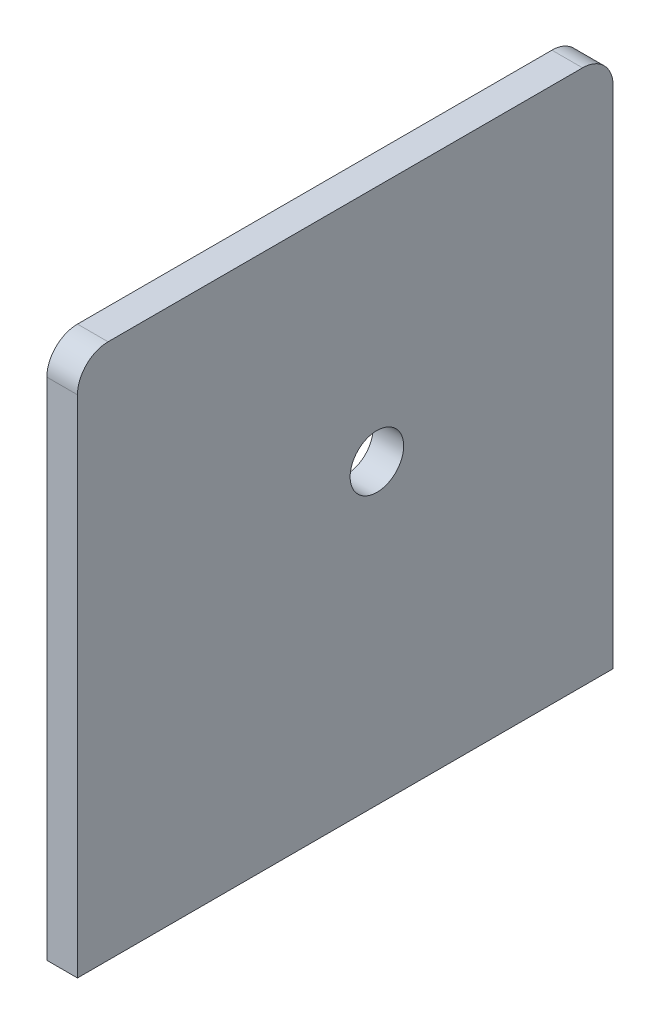
SolidWorks part; units mm, degrees
ref_plane "Front Plane" through (0, 0, 0) normal (0, 0, 1) x (1, 0, 0)
ref_plane "Top Plane" through (0, 0, 0) normal (0, 1, 0) x (1, 0, 0)
ref_plane "Right Plane" through (0, 0, 0) normal (1, 0, 0) x (0, 0, -1)
sketch "Sketch1" plane through (0, 0, 0) normal (0, 1, 0) x (1, 0, 0)
  line L6 (-24.2713, -31.1062) -> (-28.2713, -31.1062)
  line L12 (-24.2713, -31.1062) -> (-24.2713, 38.8938)
  line L13 (-24.2713, 38.8938) -> (-28.2713, 38.8938)
  line L14 (-28.2713, -31.1062) -> (-28.2713, 38.8938)
  dimension "D8" = 4
  dimension "D9" = 70
extrude "Boss-Extrude1" add sketch "Sketch1" along normal blind 3 contours L6 L14 L13 L12 | L14 L6 L12 L13 region at (-26.2713, 0, -3.8938)
extrude "Boss-Extrude2" add sketch "Sketch1<3>" along normal blind 70 rebuild error yes
sketch "Sketch1<3>" plane through (0, 0, 0) normal (0, 1, 0) x (1, 0, 0) same geometry as "Sketch1"
extrude "Boss-Extrude3" add sketch "Sketch1<4>" along normal blind 70 contours L14 L13 L12 L6
sketch "Sketch1<4>" plane through (0, 0, 0) normal (0, 1, 0) x (1, 0, 0) same geometry as "Sketch1"
sketch "Sketch5" plane through (-50.7713, 0, 0) normal (-1, 0, 0) x (0, 0, 1)
  line L0 (-8.0225, 70) -> (-8.0225, 0) construction
  line L5 (-34.2125, 70) -> (-34.2125, 3) construction
  circle A0 centre (-8.0225, 60) radius 4
  dimension "D1" = 60
  dimension "D3" = 8
  dimension "D2" = 26.19
extrude "Cut-Extrude4" cut sketch "Sketch5" against normal blind 10 rebuild error yes
sketch "Sketch6" plane through (0, 3, 0) normal (0, 1, 0) x (1, 0, 0)
  line L0 (-50.7876, 44.2125) -> (49.2124, 44.2125) construction
  line L3 (-50.7876, -35.7875) -> (49.2124, -35.7875) construction
  line L8 (-50.7713, -40.7875) -> (39.2287, -40.7875) construction
  line L9 (-50.7713, 49.2125) -> (39.2287, 49.2125) construction
  circle A0 centre (-45.7876, -35.7875) radius 2.5
  circle A1 centre (-45.7876, 44.2125) radius 2.5
  circle A2 centre (43.7185, 44.2125) radius 2.5
  circle A3 centre (43.7185, -35.7875) radius 2.5
  dimension "D1" = 5
  dimension "D2" = 5
  dimension "D3" = 5
  dimension "D4" = 5
extrude "Cut-Extrude5" cut sketch "Sketch6" against normal blind 10 rebuild error yes
extrude "Boss-Extrude4" add sketch "Sketch1<5>" along normal blind 80 rebuild error yes
sketch "Sketch1<5>" plane through (0, 0, 0) normal (0, 1, 0) x (1, 0, 0) same geometry as "Sketch1"
extrude "Cut-Extrude6" cut sketch "Sketch5<2>" against normal blind 10 rebuild error yes
sketch "Sketch5<2>" plane through (-50.7713, 0, 0) normal (-1, 0, 0) x (0, 0, 1) same geometry as "Sketch5"
fillet "Fillet1" radius 3 rebuild error yes
fillet "Fillet2" radius 5 rebuild error yes
fillet "Fillet3" radius 4 2 edges at (-26.2713, 70, -38.8938) (-26.2713, 70, 31.1062)
sketch "Sketch7" plane through (39.2287, 0, 0) normal (1, 0, 0) x (0, 0, -1)
  line L0 (-30.7875, -10) -> (39.2125, -10) construction
  line L1 (-30.7875, 65) -> (-30.7875, 3) construction
  line L2 (39.2125, 65) -> (39.2125, 3) construction
  line L3 (-37.7875, 0) -> (46.2125, 0) construction
  circle A0 centre (27.4823, -10) radius 2.5
  dimension "D1" = 10
extrude "Cut-Extrude7" cut sketch "Sketch7" against normal blind 10 rebuild error yes
sketch "Sketch8" plane through (39.2287, 0, 0) normal (1, 0, 0) x (0, 0, -1)
  line L0 (39.2125, 20) -> (-30.7875, 20) construction
  line L1 (39.2125, 65) -> (39.2125, 3) construction
  line L2 (-30.7875, 65) -> (-30.7875, 3) construction
  line L3 (26.9146, 20) -> (8.0207, 38.8939) construction
  circle A0 centre (8.0207, 38.8939) radius 2.5
  dimension "D3" = 5
  dimension "D1" = 26.72
  dimension "D2" = 45
extrude "Cut-Extrude8" cut sketch "Sketch8" against normal blind 10 rebuild error yes
sketch "Sketch9" plane through (39.2287, 0, 0) normal (1, 0, 0) x (0, 0, -1)
  circle A0 centre (8.0207, 38.8939) radius 3.5
  dimension "D1" = 7
extrude "Cut-Extrude9" cut sketch "Sketch9" against normal up to surface (67.5 mm away) up to face at (-28.2713, 45.6095, -3.8938)
sketch "Sketch26" plane through (0, 3, 0) normal (0, 1, 0) x (1, 0, 0)
  line L0 (39.2287, 39.2125) -> (39.2287, 46.2125) construction
  line L1 (39.2287, -37.7875) -> (39.2287, -30.7875) construction
  circle A0 centre (34.2287, 44.2125) radius 2.5
  circle A2 centre (34.2287, -36.0634) radius 2.5
  dimension "D1" = 5
  dimension "D2" = 5
  dimension "D3" = 5
  dimension "D4" = 5
extrude "Cut-Extrude11" cut sketch "Sketch26" against normal blind 10 contours A2 | A0 rebuild error yes
sketch "Sketch27" plane through (0, 3, 0) normal (0, 1, 0) x (1, 0, 0)
  line L0 (-49.8926, 48.3339) -> (38.35, -39.9088) construction
  line L1 (38.35, 48.3339) -> (-49.8926, -39.9088) construction
  line L2 (7.7287, 4.2125) -> (-19.2713, 4.2125) construction
  line L3 (7.7287, 3.4625) -> (-19.2713, 3.4625)
  line L4 (7.7287, 4.9625) -> (-19.2713, 4.9625)
  line L5 (0.9787, -7.4788) -> (-12.5213, 15.9039) construction
  line L6 (0.3292, -7.8538) -> (-13.1708, 15.5289)
  line L7 (1.6282, -7.1038) -> (-11.8718, 16.2789)
  line L8 (-12.5213, -7.4788) -> (0.9787, 15.9039) construction
  line L9 (-13.1708, -7.1038) -> (0.3292, 16.2789)
  line L10 (-11.8718, -7.8538) -> (1.6282, 15.5289)
  line L11 (-19.2713, 4.2125) -> (7.7287, 4.2125) construction
  line L12 (-19.2713, 4.9625) -> (7.7287, 4.9625)
  line L13 (-19.2713, 3.4625) -> (7.7287, 3.4625)
  line L14 (-12.5213, 15.9039) -> (0.9787, -7.4788) construction
  line L15 (-11.8718, 16.2789) -> (1.6282, -7.1038)
  line L16 (-13.1708, 15.5289) -> (0.3292, -7.8538)
  line L17 (0.9787, 15.9039) -> (-12.5213, -7.4788) construction
  line L18 (1.6282, 15.5289) -> (-11.8718, -7.8538)
  line L19 (0.3292, 16.2789) -> (-13.1708, -7.1038)
  arc A0 (-47.7713, 49.2125) -> (-50.7713, 46.2125) centre (-47.7713, 46.2125) ccw construction
  arc A1 (36.2287, -40.7875) -> (39.2287, -37.7875) centre (36.2287, -37.7875) ccw construction
  arc A2 (39.2287, 46.2125) -> (36.2287, 49.2125) centre (36.2287, 46.2125) ccw construction
  arc A3 (-50.7713, -37.7875) -> (-47.7713, -40.7875) centre (-47.7713, -37.7875) ccw construction
  arc A4 (7.7287, 3.4625) -> (7.7287, 4.9625) centre (7.7287, 4.2125) ccw
  arc A5 (-19.2713, 4.9625) -> (-19.2713, 3.4625) centre (-19.2713, 4.2125) ccw
  circle A9 centre (-5.7713, 4.2125) radius 5.375
  arc A10 (0.3292, -7.8538) -> (1.6282, -7.1038) centre (0.9787, -7.4788) ccw
  arc A11 (-11.8718, 16.2789) -> (-13.1708, 15.5289) centre (-12.5213, 15.9039) ccw
  arc A12 (-13.1708, -7.1038) -> (-11.8718, -7.8538) centre (-12.5213, -7.4788) ccw
  arc A13 (1.6282, 15.5289) -> (0.3292, 16.2789) centre (0.9787, 15.9039) ccw
  arc A14 (-19.2713, 4.9625) -> (-19.2713, 3.4625) centre (-19.2713, 4.2125) ccw
  arc A15 (7.7287, 3.4625) -> (7.7287, 4.9625) centre (7.7287, 4.2125) ccw
  arc A16 (-11.8718, 16.2789) -> (-13.1708, 15.5289) centre (-12.5213, 15.9039) ccw
  arc A17 (0.3292, -7.8538) -> (1.6282, -7.1038) centre (0.9787, -7.4788) ccw
  arc A18 (1.6282, 15.5289) -> (0.3292, 16.2789) centre (0.9787, 15.9039) ccw
  arc A19 (-13.1708, -7.1038) -> (-11.8718, -7.8538) centre (-12.5213, -7.4788) ccw
  circle A20 centre (-5.7713, 4.2125) radius 2.75
  point P18 (-5.7713, 4.2125)
  point P30 (-5.7713, 4.2125)
  point P37 (-5.7713, 4.2125)
  point P44 (-5.7713, 4.2125)
  point P51 (-5.7713, 4.2125)
  point P58 (-5.7713, 4.2125)
  point P63 (-5.7713, 4.2125)
  dimension "D1" = 10.75
  dimension "D2" = 0.75
  dimension "D3" = 13.5
  dimension "D4" = 6
extrude "Cut-Extrude14" cut sketch "Sketch27" against normal blind 10 contours L3 A5 L4 A4 | L6 A11 L7 A10 | L10 A13 L9 A12 rebuild error yes
extrude "Cut-Extrude15" cut sketch "Sketch27<7>" against normal blind 10 contours L3 A20 L9 | L6 A20 L4 | L9 A20 L7 | L4 A20 L10 | L7 A20 L3 | L10 A20 L6 rebuild error yes
sketch "Sketch27<7>" plane through (0, 3, 0) normal (0, 1, 0) x (1, 0, 0) same geometry as "Sketch27"
sketch "Sketch28" plane through (-50.7713, 0, 0) normal (-1, 0, 0) x (0, 0, 1)
  line L0 (-23.4588, 51.635) -> (-8.5312, 68.47)
  line L1 (-8.5312, 68.47) -> (0.4475, 60.5086)
  line L2 (0.4475, 60.5086) -> (-14.4801, 43.6736)
  line L3 (-14.4801, 43.6736) -> (-23.4588, 51.635)
  line L4 (-8.0225, 60) -> (-12.6884, 54.7379) construction
  line L5 (-12.6884, 54.7379) -> (-25.2505, 40.5707) construction
  line L6 (-8.0225, 60) -> (2.1094, 71.4266) construction
  circle A0 centre (-8.0225, 60) radius 4 construction
  circle A1 centre (-8.0225, 60) radius 4
  circle A2 centre (-2.3169, 66.4347) radius 1
  circle A3 centre (-20.6944, 45.709) radius 1
  point P8 (-18.9694, 47.6543)
  dimension "D3" = 2
  dimension "D4" = 8.6
  dimension "D5" = 27.7
  dimension "D1" = 22.5
  dimension "D2" = 12
  dimension "D6" = 2.6
extrude "Cut-Extrude16" cut sketch "Sketch28" against normal up to surface (4 mm away) rebuild error yes
sketch "Sketch29" plane through (39.2287, 0, 0) normal (1, 0, 0) x (0, 0, -1)
  line L8 (8.0207, 38.8939) -> (0.0593, 47.8726) construction
  line L9 (0.0593, 47.8726) -> (37.8759, 5.2239) construction
  line L10 (8.5294, 47.3639) -> (23.457, 30.5289)
  line L11 (23.457, 30.5289) -> (14.4783, 22.5675)
  line L12 (14.4783, 22.5675) -> (-0.4493, 39.4025)
  line L13 (-0.4493, 39.4025) -> (8.5294, 47.3639)
  circle A6 centre (8.0207, 38.8939) radius 3.5 construction
  circle A7 centre (8.0207, 38.8939) radius 3.5
  circle A8 centre (2.3151, 45.3286) radius 1
  circle A9 centre (20.6926, 24.6028) radius 1
  point P4 (4.04, 43.3832)
  point P28 (18.9676, 26.5482)
  dimension "D4" = 2.6
  dimension "D5" = 27.7
  dimension "D6" = 2
  dimension "D7" = 2
  dimension "D2" = 12
  dimension "D3" = 22.5
  dimension "D8" = 8.6
extrude "Cut-Extrude18" cut sketch "Sketch29" against normal up to surface (4 mm away) rebuild error yes
sketch "Sketch31" plane through (0, 3, 0) normal (0, 1, 0) x (1, 0, 0)
  circle A0 centre (-5.7713, 4.2125) radius 5.375
  dimension "D1" = 10.75
extrude "Cut-Extrude19" cut sketch "Sketch31" against normal blind 10 rebuild error yes
